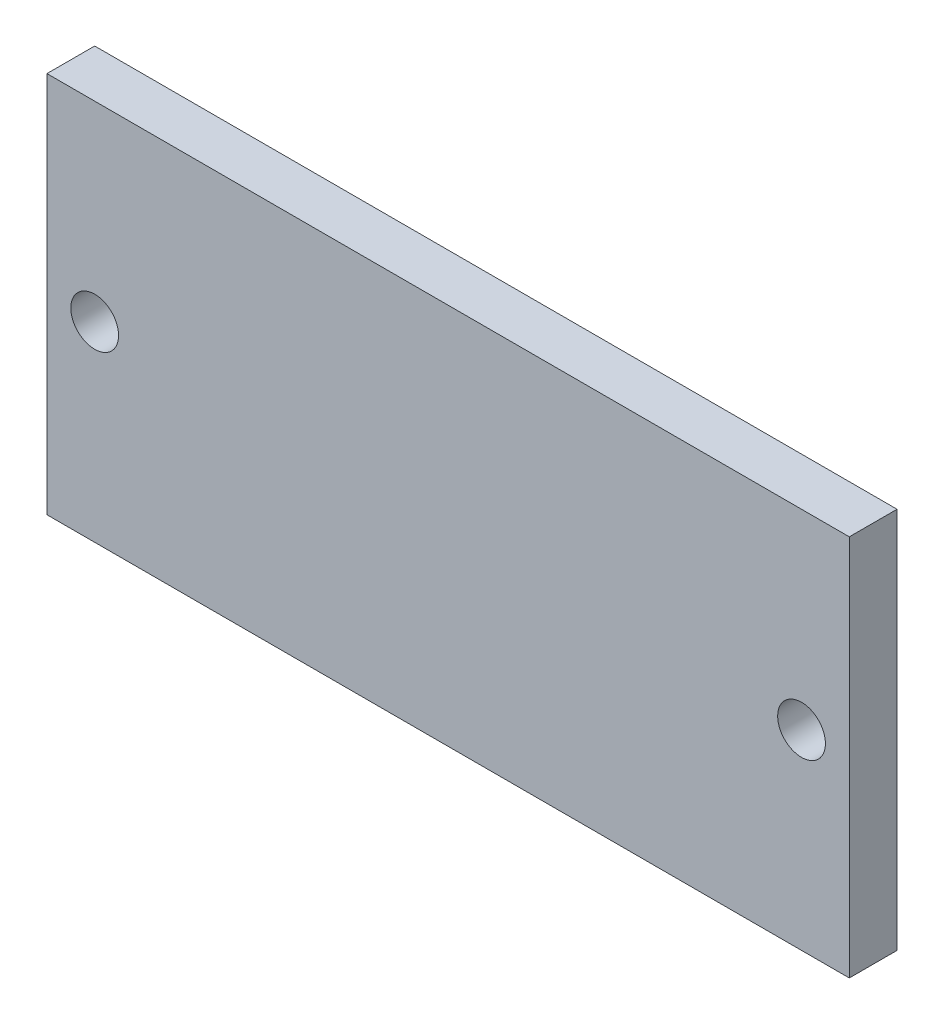
SolidWorks part; units mm, degrees
ref_plane "Front Plane" through (0, 0, 0) normal (0, 0, 1) x (1, 0, 0)
ref_plane "Top Plane" through (0, 0, 0) normal (0, 1, 0) x (1, 0, 0)
ref_plane "Right Plane" through (0, 0, 0) normal (1, 0, 0) x (0, 0, -1)
sketch "Sketch1" plane through (0, 0, 0) normal (0, 0, 1) x (1, 0, 0)
  line L0 (-26.67, 0) -> (26.67, 0) construction
  line L1 (26.67, -12.7) -> (-26.67, -12.7)
  line L2 (26.67, -12.7) -> (26.67, 12.7)
  line L3 (26.67, 12.7) -> (-26.67, 12.7)
  line L4 (-26.67, -12.7) -> (-26.67, 12.7)
  line L5 (0, 12.7) -> (0, -12.7) construction
  circle A0 centre (-23.495, 0) radius 1.5875
  circle A1 centre (23.495, 0) radius 1.5875
  dimension "D3" = 3.175
  dimension "D1" = 53.34
  dimension "D2" = 25.4
  dimension "D4" = 3.175
extrude "Boss-Extrude1" add sketch "Sketch1" along normal blind 3.175
